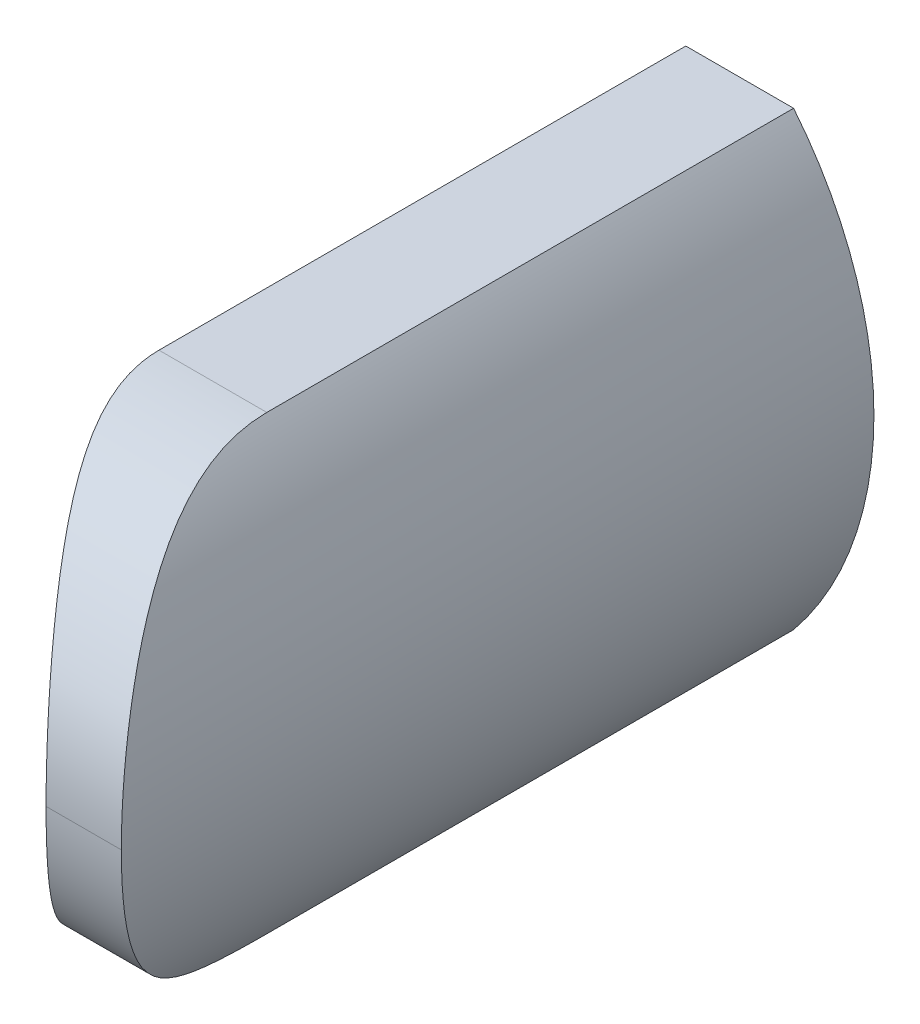
SolidWorks part; units mm, degrees
ref_plane "Plan de face" through (0, 0, 0) normal (0, 0, 1) x (1, 0, 0)
ref_plane "Plan de dessus" through (0, 0, 0) normal (0, 1, 0) x (1, 0, 0)
ref_plane "Plan de droite" through (0, 0, 0) normal (1, 0, 0) x (0, 0, -1)
sketch "Esquisse1" plane through (0, 0, 0) normal (0, 0, 1) x (1, 0, 0)
  line L0 (22.5, 30) -> (22.5, -30)
  line L1 (22.5, 30) -> (36.8273, 30)
  line L2 (22.5, -30) -> (36.8273, -30)
  circle A0 centre (0, 0) radius 50
  circle A1 centre (0, 0) radius 47.5
  circle A2 centre (0, 0) radius 37.5
  dimension "D1" = 100
  dimension "D2" = 2.5
  dimension "D3" = 10
  dimension "D4" = 60
extrude "Boss.-Extru.1" add sketch "Esquisse1" along normal blind 100 contours A2 L2 A1 L1 region at (38.1648, 0, 0)
fillet "Congé1" radius 30 2 edges at (29.6636, 30, 100) (29.6636, -30, 100)
